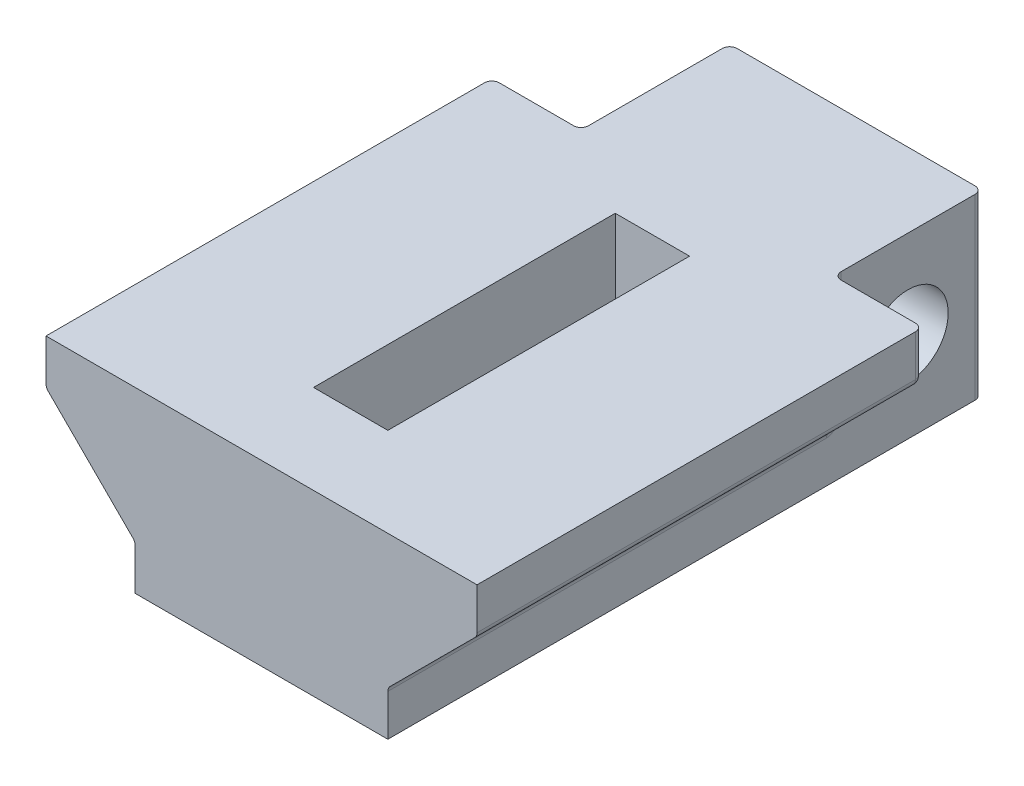
SolidWorks part; units mm, degrees
material "ABS"
ref_plane "Front Plane" through (0, 0, 0) normal (0, 0, 1) x (1, 0, 0)
ref_plane "Top Plane" through (0, 0, 0) normal (0, 1, 0) x (1, 0, 0)
ref_plane "Right Plane" through (0, 0, 0) normal (1, 0, 0) x (0, 0, -1)
sketch "Sketch1" plane through (0, 0, 0) normal (0, 0, 1) x (1, 0, 0)
  line L0 (0, 0) -> (0, 12) construction
  line L1 (-14.5, 12) -> (-14.5, 9)
  line L2 (-14.5, 9) -> (-8.5, 3)
  line L3 (-8.5, 3) -> (-8.5, 0)
  line L4 (8.5, 3) -> (8.5, 0)
  line L5 (14.5, 9) -> (8.5, 3)
  line L6 (14.5, 12) -> (14.5, 9)
  line L7 (-14.5, 12) -> (14.5, 12)
  line L8 (-8.5, 0) -> (8.5, 0)
  dimension "D1" = 12
  dimension "D2" = 3
  dimension "D3" = 45
  dimension "D4" = 17
extrude "Dovetail Body" add sketch "Sketch1" along normal mid plane 40
sketch "Sketch9" plane through (0, 0, -20) normal (0, 0, -1) x (-1, 0, 0)
  line L0 (0, 12) -> (0, 0) construction
  line L1 (-14.5, 12) -> (-8.5, 12)
  line L2 (-14.5, 12) -> (-14.5, 0)
  line L3 (-14.5, 0) -> (-8.5, 0)
  line L4 (-8.5, 12) -> (-8.5, 0)
  line L5 (-14.5, 12) -> (14.5, 12) construction
  line L6 (8.5, 0) -> (-8.5, 0) construction
  line L7 (8.5, 12) -> (8.5, 0)
  line L8 (14.5, 0) -> (8.5, 0)
  line L9 (14.5, 12) -> (14.5, 0)
  line L10 (14.5, 12) -> (8.5, 12)
extrude "Bolt Clearance" cut sketch "Sketch9" against normal blind 10
sketch "Sketch10" plane through (8.5, 0, 0) normal (1, 0, 0) x (0, 0, -1)
  line L0 (15, 12) -> (15, 0) construction
  line L1 (10, 12) -> (20, 12) construction
  line L2 (-20, 0) -> (20, 0) construction
  circle A0 centre (15, 6) radius 2.7
  dimension "D1" = 5.4
extrude "Bolt Insert" cut sketch "Sketch10" against normal through all
sketch "Sketch11" plane through (0, 0, 0) normal (0, -1, 0) x (1, 0, 0)
  line L0 (0, -6.3) -> (0, 0) construction
  line L1 (2.5, -6.3) -> (-2.5, -6.3)
  line L2 (2.5, -6.3) -> (2.5, 14)
  line L3 (2.5, 14) -> (-2.5, 14)
  line L4 (-2.5, -6.3) -> (-2.5, 14)
  line L5 (8.5, 20) -> (8.5, -20) construction
  line L6 (-8.5, 20) -> (8.5, 20) construction
  line L7 (8.5, -17.7) -> (8.5, -12.3) construction
  line L8 (8.5, -17.7) -> (8.5, -12.3) construction
  dimension "D1" = 6
  dimension "D2" = 6
  dimension "D3" = 6
extrude "Weight Clearance" cut sketch "Sketch11" against normal through all
fillet "Contouring" radius 0.5 12 edges at (8.5, 7.5, -10) (-8.5, 7.5, -10) (8.5, 3, 5) (-8.5, 3, 5) (-14.5, 9, 5) (14.5, 9, 5) (-11.5, 6, -10) (-14.5, 10.5, -10) (-8.5, 6, -20) (8.5, 6, -20) (11.5, 6, -10) (14.5, 10.5, -10)
equation "\"width keep\"= 3"
equation "\"dovetail height\"= 12"
equation "\"dovetail angle\"= 45"
equation "\"dovetail width\" = 17"
equation "\"D1@Sketch1\"=\"dovetail height\""
equation "\"D2@Sketch1\"=\"width keep\""
equation "\"D3@Sketch1\"=\"dovetail angle\""
equation "\"D4@Sketch1\"=\"dovetail width\""
equation "\"dovetail length\"= 40"
equation "\"D1@Dovetail Body\" = \"dovetail length\""
equation "\"print free\"= 0.35"
equation "\"print fit\"= 0.15"
equation "\"D1@Sketch11\"=2*\"width keep\""
equation "\"D2@Sketch11\"=\"D1@Sketch11\""
equation "\"D3@Sketch11\"=\"D2@Sketch11\""
